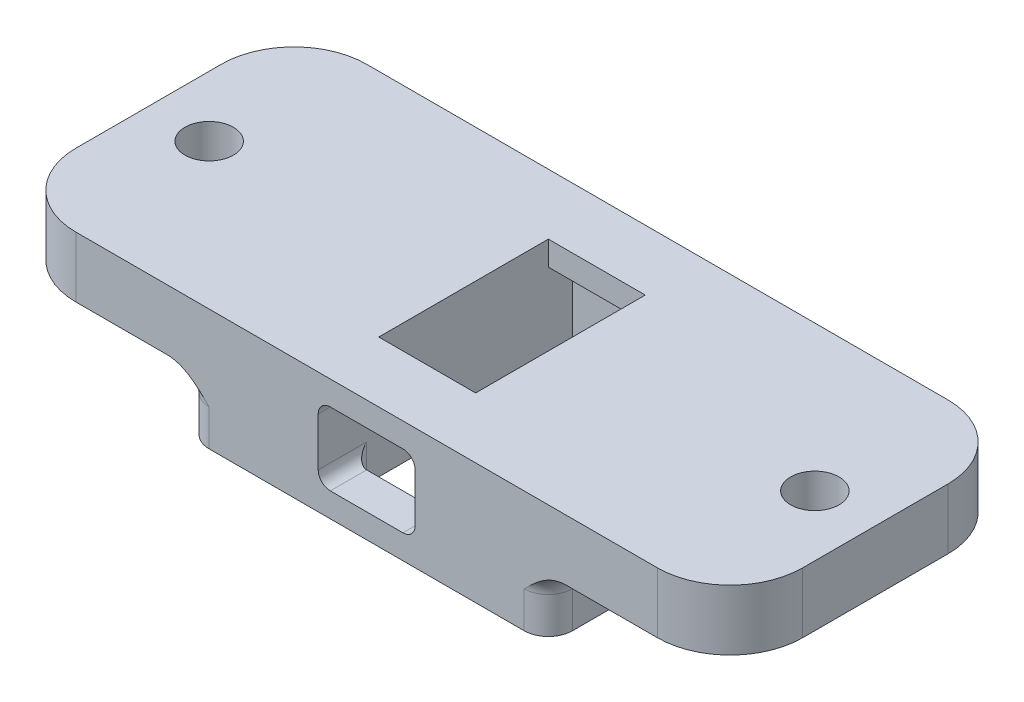
SolidWorks part; units mm, degrees
ref_plane "Front Plane" through (0, 0, 0) normal (0, 0, 1) x (1, 0, 0)
ref_plane "Top Plane" through (0, 0, 0) normal (0, 1, 0) x (1, 0, 0)
ref_plane "Right Plane" through (0, 0, 0) normal (1, 0, 0) x (0, 0, -1)
sketch "Sketch1" plane through (0, 0, 0) normal (0, 1, 0) x (1, 0, 0)
  line L1 (-5.08, 11.43) -> (5.08, 11.43)
  line L2 (-5.08, 11.43) -> (-5.08, -11.43)
  line L3 (-5.08, -11.43) -> (5.08, -11.43)
  line L4 (5.08, 11.43) -> (5.08, -11.43)
  line L5 (-5.08, 11.43) -> (5.08, -11.43) construction
  line L6 (-5.08, -11.43) -> (5.08, 11.43) construction
  line L7 (-19.05, 15.24) -> (19.05, 15.24)
  line L8 (-19.05, 15.24) -> (-19.05, -15.24)
  line L9 (-19.05, -15.24) -> (19.05, -15.24)
  line L10 (19.05, 15.24) -> (19.05, -15.24)
  line L11 (-19.05, 15.24) -> (19.05, -15.24) construction
  line L12 (-19.05, -15.24) -> (19.05, 15.24) construction
  circle A0 centre (-12.7, 0) radius 2.54
  circle A1 centre (12.7, 0) radius 2.54
  point P0 (0, 0)
  point P6 (0, 0)
  dimension "D5" = 5.08
  dimension "D6" = 5.08
  dimension "D1" = 10.16
  dimension "D2" = 22.86
  dimension "D3" = 12.7
  dimension "D4" = 12.7
  dimension "D7" = 38.1
  dimension "D8" = 30.48
extrude "Boss-Extrude1" add sketch "Sketch1" against normal blind 12.7 contours L10 L7 L8 L9 A1 A0 L1 L4 L3 L2 region at (0, 0, -14.7521)
sketch "Sketch2" plane through (0, 0, -11.43) normal (0, 0, 1) x (1, 0, 0)
  line L0 (5.08, -12.7) -> (5.08, 0) construction
  line L1 (-5.08, 0) -> (5.08, 0)
  line L2 (-5.08, 0) -> (-5.08, -2.54)
  line L3 (-5.08, -2.54) -> (5.08, -2.54)
  line L4 (5.08, 0) -> (5.08, -2.54)
  dimension "D1" = 2.54
extrude "Boss-Extrude2" add sketch "Sketch2" along normal blind 2.54
sketch "Sketch3" plane through (0, 0, 11.43) normal (0, 0, -1) x (-1, 0, 0)
  line L0 (-5.08, -12.7) -> (-5.08, 0) construction
  line L1 (5.08, 0) -> (-5.08, 0)
  line L2 (5.08, 0) -> (5.08, -2.54)
  line L3 (5.08, -2.54) -> (-5.08, -2.54)
  line L4 (-5.08, 0) -> (-5.08, -2.54)
  dimension "D1" = 2.54
extrude "Boss-Extrude3" add sketch "Sketch3" along normal blind 2.54
fillet "Fillet1" radius 2.54 4 edges at (-19.05, -6.35, 15.24) (19.05, -6.35, 15.24) (19.05, -6.35, -15.24) (-19.05, -6.35, -15.24)
sketch "Sketch4" plane through (0, 0, 11.43) normal (0, 0, -1) x (-1, 0, 0)
  line L6 (5.08, -12.7) -> (5.08, -2.54) construction
  line L7 (-5.08, -2.54) -> (5.08, -2.54)
  line L8 (-5.08, -2.54) -> (-5.08, -10.16)
  line L9 (-5.08, -10.16) -> (5.08, -10.16)
  line L10 (5.08, -2.54) -> (5.08, -10.16)
  dimension "D1" = 7.62
extrude "Cut-Extrude1" cut sketch "Sketch4" against normal through all
fillet "Fillet2" radius 1.27 6 edges at (5.08, -11.43, 11.43) (-5.08, -11.43, 11.43) (5.08, -10.16, 13.335) (-5.08, -10.16, 13.335) (-5.08, -2.54, 12.065) (5.08, -2.54, 12.065)
sketch "Sketch5" plane through (0, 0, 0) normal (0, 1, 0) x (1, 0, 0)
  line L0 (-16.51, 15.24) -> (16.51, 15.24) construction
  line L1 (-38.1, 15.24) -> (38.1, 15.24)
  line L2 (-38.1, 15.24) -> (-38.1, -15.24)
  line L3 (-38.1, -15.24) -> (38.1, -15.24)
  line L4 (38.1, 15.24) -> (38.1, -15.24)
  line L5 (-38.1, 15.24) -> (38.1, -15.24) construction
  line L6 (-38.1, -15.24) -> (38.1, 15.24) construction
  line L7 (-5.08, 11.43) -> (5.08, 11.43) construction
  line L8 (-5.08, 11.43) -> (5.08, 11.43)
  line L9 (-5.08, 11.43) -> (-5.08, -15.24)
  line L10 (-5.08, -15.24) -> (5.08, -15.24)
  line L11 (5.08, 11.43) -> (5.08, -15.24)
  point P0 (0, 0)
  line M3 (-5.08, -8.89) -> (-5.08, 8.89)
  line M4 (-5.08, 8.89) -> (5.08, 8.89)
  line M5 (5.08, 8.89) -> (5.08, -8.89)
  line M6 (5.08, -8.89) -> (-5.08, -8.89)
  circle M7 centre (12.7, 0) radius 2.54
  circle M8 centre (-12.7, 0) radius 2.54
  line M9 (-19.05, 12.7) -> (-19.05, -12.7)
  arc M10 (-19.05, -12.7) -> (-16.51, -15.24) centre (-16.51, -12.7) ccw
  line M11 (-16.51, -15.24) -> (16.51, -15.24)
  arc M12 (16.51, -15.24) -> (19.05, -12.7) centre (16.51, -12.7) ccw
  line M13 (19.05, -12.7) -> (19.05, 12.7)
  arc M14 (19.05, 12.7) -> (16.51, 15.24) centre (16.51, 12.7) ccw
  line M15 (16.51, 15.24) -> (-16.51, 15.24)
  arc M16 (-16.51, 15.24) -> (-19.05, 12.7) centre (-16.51, 12.7) ccw
  dimension "D1" = 76.2
extrude "Boss-Extrude4" add sketch "Sketch5" against normal blind 6.35 contours L2 L3 L1 M10 M9 M16 | M16 M9 M10 M11 M12 M13 M14 M15 M8 M7 M6 M3 M4 M5 | L4 L1 L3 M14 M13 M12 | M8 | M7 region at (-28.5271, 0, 0) region at (0, 0, -14.7521) region at (28.5271, 0, 0) region at (12.7, 0, 0) region at (-12.7, 0, 0)
sketch "Sketch6" plane through (0, 0, 0) normal (0, 1, 0) x (1, 0, 0)
  circle A0 centre (-31.75, 0) radius 2.54
  circle A1 centre (31.75, 0) radius 2.54
  dimension "D3" = 5.08
  dimension "D4" = 5.08
  dimension "D1" = 31.75
  dimension "D2" = 31.75
extrude "Cut-Extrude2" cut sketch "Sketch6" against normal through all
fillet "Fillet3" radius 7.62 4 edges at (38.1, -3.175, -15.24) (38.1, -3.175, 15.24) (-38.1, -3.175, 15.24) (-38.1, -3.175, -15.24)
fillet "Fillet4" radius 2.54 6 edges at (-18.3061, -6.35, 14.4961) (-18.3061, -6.35, -14.4961) (18.3061, -6.35, 14.4961) (18.3061, -6.35, -14.4961) (-19.05, -6.35, 0) (19.05, -6.35, 0)
